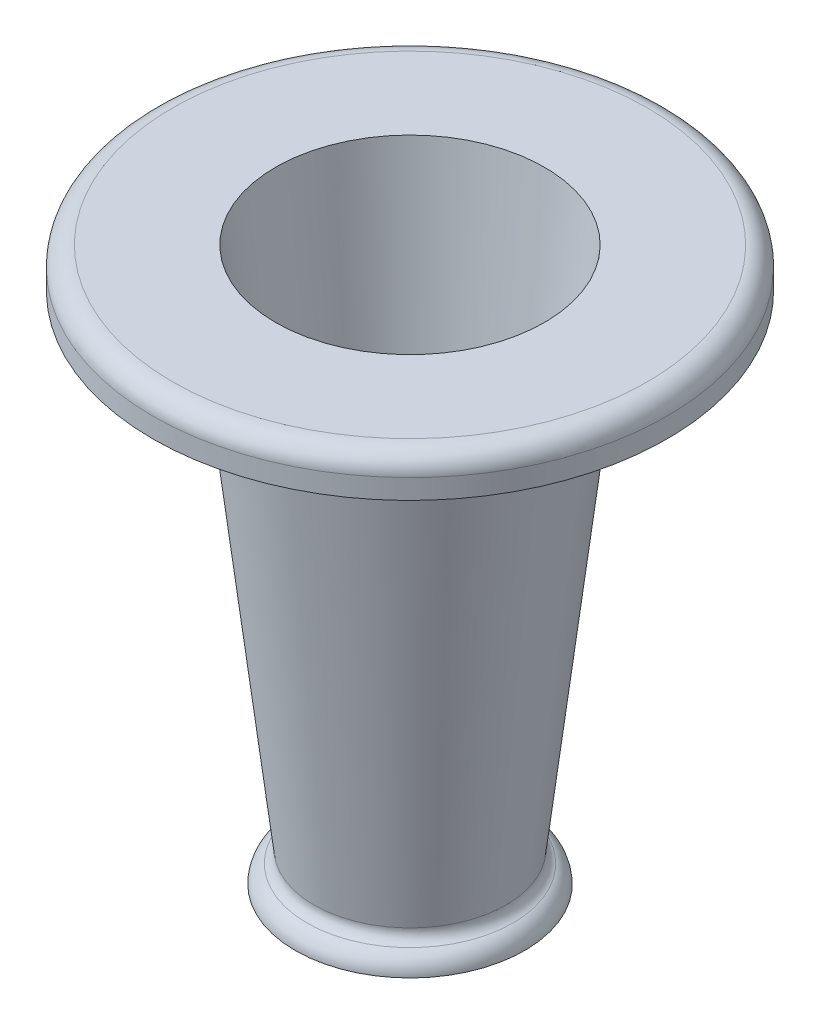
SolidWorks part; units mm, degrees
ref_plane "Alzado" through (0, 0, 0) normal (0, 0, 1) x (1, 0, 0)
ref_plane "Planta" through (0, 0, 0) normal (0, 1, 0) x (1, 0, 0)
ref_plane "Vista lateral" through (0, 0, 0) normal (1, 0, 0) x (0, 0, -1)
sketch "Croquis1" plane through (0, 0, 0) normal (0, 1, 0) x (1, 0, 0)
  circle A0 centre (0, 0) radius 29
  dimension "D1" = 58
extrude "Saliente-Extruir1" add sketch "Croquis1" along normal blind 5
sketch "Croquis2" plane through (0, 5, 0) normal (0, 1, 0) x (1, 0, 0)
  circle A0 centre (0, 0) radius 24
  dimension "D1" = 48
ref_plane "Plano1" through (0, 135, 0) normal (0, 1, 0) x (1, 0, 0)
sketch "Croquis3" plane through (0, 135, 0) normal (0, 1, 0) x (1, 0, 0)
  circle A0 centre (0, 0) radius 39
  dimension "D1" = 78
loft "Recubrir1" add profiles "Croquis2", "Croquis3" connector at (-20.2477, 5, 12.8853) connector at (-32.5963, 135, 21.4122)
sketch "Croquis4" plane through (0, 135, 0) normal (0, 1, 0) x (1, 0, 0)
  circle A0 centre (0, 0) radius 65
  dimension "D1" = 130
extrude "Saliente-Extruir2" add sketch "Croquis4" along normal blind 5
sketch "Croquis5" plane through (0, 135, 0) normal (0, -1, 0) x (1, 0, 0)
  circle A0 centre (0, 0) radius 65 construction
  circle A1 centre (0, 0) radius 65
  circle A2 centre (0, 0) radius 62.5
  dimension "D1" = 125
extrude "Saliente-Extruir3" add sketch "Croquis5" along normal blind 5
fillet "Redondeo1" radius 5 3 edges at (0, 135, -62.5) (0, 140, 65) (0, 5, 29)
sketch "Croquis6" plane through (0, 0, 0) normal (0, -1, 0) x (1, 0, 0)
  circle A0 centre (0, 0) radius 23
  dimension "D1" = 46
extrude "Cortar-Extruir1" cut sketch "Croquis6" against normal blind 62
ref_axis "Eje1" through (0, 192.8216, 0) along (0, -1, 0)
sketch "Croquis7" plane through (0, 0, 0) normal (0, 0, 1) x (1, 0, 0)
  line L0 (0, 37.9521) -> (0, 140)
  line L1 (0, 192.8216) -> (0, 6.2726) construction
  line L2 (60, 140) -> (-60, 140) construction
  line L3 (0, 140) -> (34, 140)
  line L4 (34, 140) -> (22, 37.9521)
  line L5 (22, 37.9521) -> (0, 37.9521)
  dimension "D1" = 34
  dimension "D2" = 22
  dimension "D3" = 102.0479
revolve "Cortar-Revolución1" cut sketch "Croquis7" angle 360 about axis through (0, 192.8216, 0) along (0, -1, 0) region at (14.2143, 92.6206, 0)
fillet "Redondeo2" radius 3 1 edges at (0, 5, 24)
